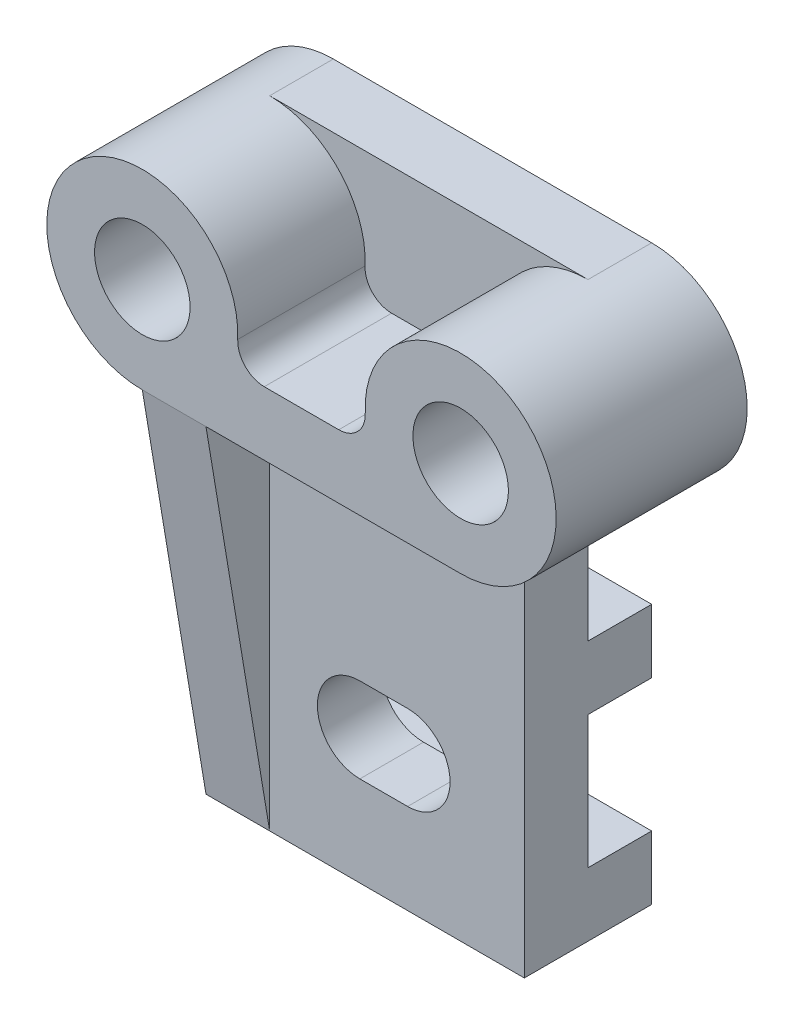
SolidWorks part; units mm, degrees
material "AISI 304"
ref_plane "Front Plane" through (0, 0, 0) normal (1, 0, 0) x (0, 1, 0)
ref_plane "Top Plane" through (0, 0, 0) normal (0, 0, 1) x (0, 1, 0)
ref_plane "Right Plane" through (0, 0, 0) normal (0, 1, 0) x (-1, 0, 0)
sketch "Sketch1" plane through (0, 0, 0) normal (0, 0, 1) x (0, 1, 0)
  line L0 (27, 30) -> (27, -30)
  line L1 (45, -30) -> (-45, -30)
  line L2 (45, -30) -> (45, 30)
  line L3 (45, 30) -> (-45, 30)
  line L4 (-45, -30) -> (-45, 30)
  line L5 (45, -30) -> (-45, 30) construction
  line L6 (45, 30) -> (-45, -30) construction
  line L7 (39, 30) -> (39, -30)
  line L8 (63, 30) -> (63, -30)
  line L9 (-20, -8) -> (-20, 1) construction
  line L10 (-45, -30) -> (-20, -30) construction
  line L11 (-45, -30) -> (-45, -8) construction
  line L12 (-45, -8) -> (-20, -8) construction
  line L13 (-20, -30) -> (-20, -8) construction
  line L14 (-28, 1) -> (-28, -8)
  line L15 (-12, -8) -> (-12, 1)
  line L17 (-45, 30) -> (27, 30)
  line L18 (-45, 30) -> (-45, 18)
  line L19 (-45, 18) -> (27, 18)
  line L20 (27, 30) -> (27, 18)
  line L21 (-45, -30) -> (-33, -30)
  line L22 (-45, -30) -> (-45, 30)
  line L23 (-45, 30) -> (-33, 30)
  line L24 (-33, -30) -> (-33, 30)
  line L25 (-33, -30) -> (-8, -30)
  line L26 (-33, -30) -> (-33, 30)
  line L27 (-33, 30) -> (-8, 30)
  line L28 (-8, -30) -> (-8, 30)
  line L29 (-8, 30) -> (4, 30)
  line L30 (-8, 30) -> (-8, -30)
  line L31 (-8, -30) -> (4, -30)
  line L32 (4, 30) -> (4, -30)
  line L33 (4, -30) -> (27, -30)
  line L34 (4, -30) -> (4, 30)
  line L35 (4, 30) -> (27, 30)
  line L36 (27, -30) -> (27, 30)
  circle A0 centre (45, 30) radius 9
  circle A1 centre (45, -30) radius 9
  circle A2 centre (45, 30) radius 18
  circle A3 centre (45, -30) radius 18
  circle A4 centre (-20, -8) radius 8
  circle A5 centre (-20, 1) radius 8
  point P0 (0, 0)
  dimension "D3" = 18
  dimension "D4" = 36
  dimension "D9" = 16
  dimension "D1" = 90
  dimension "D2" = 60
  dimension "D6" = 25
  dimension "D7" = 22
  dimension "D8" = 9
  dimension "D10" = 12
  dimension "D11" = 12
  dimension "D12" = 37
  dimension "D13" = 12
  dimension "D14" = 23
  dimension "D5" = 12
extrude "Boss-Extrude1" add sketch "Sketch1" along normal blind 36 contours A3 L2 A1 L1 | L7 A3 L1 A1 | L2 A3 L7 A1 | A3 L7 A2 L0 | L3 A2 L7 A0 | L2 A2 L3 A0 | L7 A2 L2 A0 region at (0, 32.2772, 0) region at (-47.4909, 45, 0) region at (-22.7767, 33.6408, 0) region at (-17.0484, 41.9362, 0) region at (22.7767, 33.6408, 0) region at (30.5091, 31.5, 0) region at (17.0484, 41.9362, 0)
extrude "Boss-Extrude2" add sketch "Sketch1<4>" along normal blind 12 contours A3 L2 A2 L7 | A3 L8 A2 L2 region at (0, 55.2126, 0) region at (0, 41.9585, 0)
sketch "Sketch1<4>" plane through (0, 0, 0) normal (0, 0, 1) x (0, 1, 0) same geometry as "Sketch1"
extrude "Boss-Extrude4" add sketch "Sketch1<6>" along normal blind 24 contours L32 L19 L28 L1 | L1 L28 L19 L24 A5 L15 A4 L14 | L19 L32 L1 L0 | L1 L24 L19 L4 | L3 L32 L19 L0 | L32 L17 L28 L19 | L19 L28 L17 L24 | L19 L24 L17 L4 region at (-24, 15.5, 0) region at (6, 15.5, 0) region at (-24, -2, 0) region at (6, -2, 0) region at (-24, -20.5, 0) region at (6, -8.5412, 0) region at (-24, -39, 0) region at (6, -39, 0)
sketch "Sketch1<6>" plane through (0, 0, 0) normal (0, 0, 1) x (0, 1, 0) same geometry as "Sketch1"
extrude "Cut-Extrude2" cut sketch "Sketch1<8>" along normal blind 12 contours L19 L28 L17 L24 | L1 L28 L19 L24 A5 L15 A4 L14 | L3 L32 L19 L0 | L19 L32 L1 L0 region at (-24, 15.5, 0) region at (6, 15.5, 0) region at (-24, -20.5, 0) region at (6, -8.5412, 0)
sketch "Sketch1<8>" plane through (0, 0, 0) normal (0, 0, 1) x (0, 1, 0) same geometry as "Sketch1"
extrude "Boss-Extrude5" add sketch "Sketch1<10>" along normal blind 12 from offset 24 contours L3 L32 L19 L0 | L32 L17 L28 L19 | L19 L28 L17 L24 | L19 L24 L17 L4 region at (-24, 15.5, 0) region at (-24, -2, 0) region at (-24, -20.5, 0) region at (-24, -39, 0)
sketch "Sketch1<10>" plane through (0, 0, 0) normal (0, 0, 1) x (0, 1, 0) same geometry as "Sketch1"
sketch "Sketch2" plane through (-18, 0, 0) normal (1, 0, 0) x (0, 1, 0)
  line L0 (-45, 24) -> (27, 36)
  line L1 (27, 36) -> (27, 24)
  line L2 (27, 24) -> (-45, 24)
  line L3 (-45, 24) -> (-45, 36)
  line L4 (-45, 36) -> (27, 36)
  line M3 (27, 36) -> (-45, 36)
  line M4 (-45, 36) -> (-45, 24)
extrude "Cut-Extrude3" cut sketch "Sketch2" against normal blind 12 contours L0 M4 M3 region at (-18, -21, 32)
fillet "Fillet1" radius 5 2 edges at (-13.0294, 39, 24) (13.0294, 39, 24)
